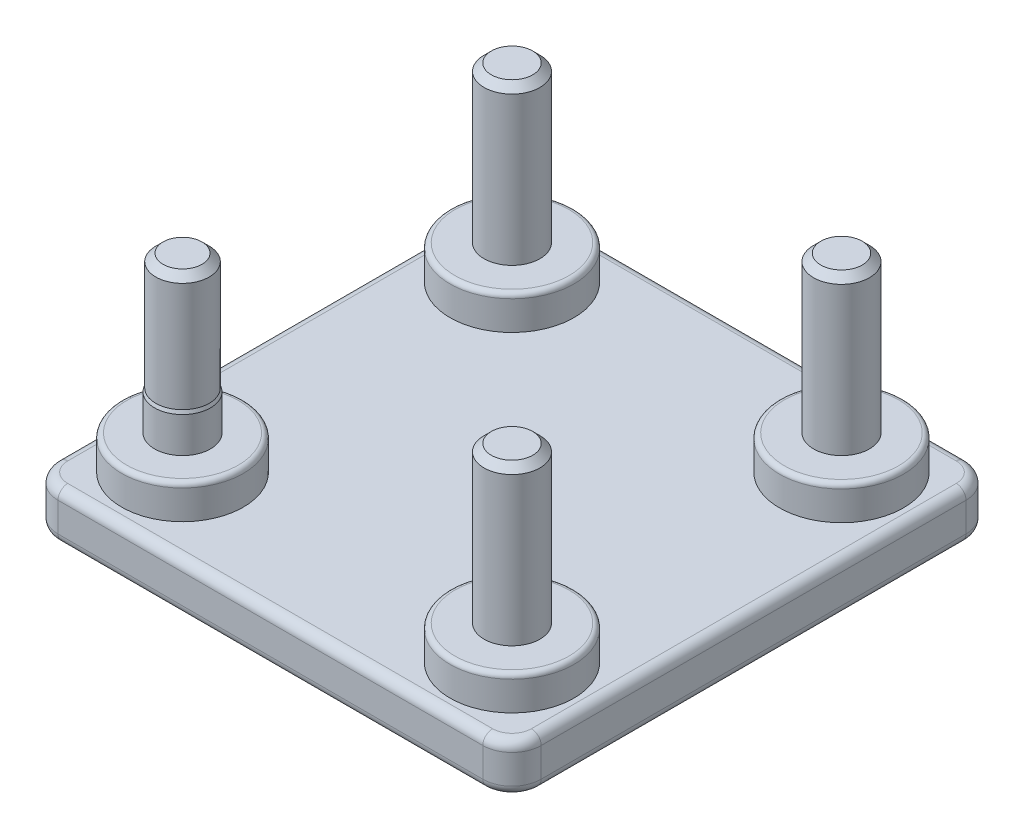
SolidWorks part; units mm, degrees
ref_plane "Front Plane" through (0, 0, 0) normal (0, 0, 1) x (1, 0, 0)
ref_plane "Top Plane" through (0, 0, 0) normal (0, 1, 0) x (1, 0, 0)
ref_plane "Right Plane" through (0, 0, 0) normal (1, 0, 0) x (0, 0, -1)
sketch "Sketch1" plane through (0, 0, 0) normal (0, 1, 0) x (1, 0, 0)
  line L1 (0.1721, 16.4036) -> (49.8471, 16.4036)
  line L2 (0.1721, 16.4036) -> (0.1721, 66.0786)
  line L3 (0.1721, 66.0786) -> (49.8471, 66.0786)
  line L4 (49.8471, 16.4036) -> (49.8471, 66.0786)
  line L8 (14.7548, 29.4959) -> (35.2548, 29.4959)
  line L9 (13.2548, 51.4959) -> (13.2548, 30.9959)
  line L10 (35.2548, 52.9959) -> (14.7548, 52.9959)
  line L11 (36.7548, 30.9959) -> (36.7548, 51.4959)
  line L12 (14.7548, 29.4959) -> (35.2548, 29.4959) construction
  line L13 (13.2548, 51.4959) -> (13.2548, 30.9959) construction
  line L14 (35.2548, 52.9959) -> (14.7548, 52.9959) construction
  line L15 (36.7548, 30.9959) -> (36.7548, 51.4959) construction
  line L16 (14.0048, 34.5935) -> (18.0048, 34.5935)
  line L17 (14.0048, 47.8007) -> (14.0048, 34.5935)
  line L18 (18.0048, 47.8007) -> (14.0048, 47.8007)
  line L19 (18.0048, 34.5935) -> (18.0048, 47.8007)
  line L20 (14.0048, 34.5935) -> (18.0048, 34.5935) construction
  line L21 (14.0048, 47.8007) -> (14.0048, 34.5935) construction
  line L22 (18.0048, 47.8007) -> (14.0048, 47.8007) construction
  line L23 (18.0048, 34.5935) -> (18.0048, 47.8007) construction
  line L24 (32.0048, 34.5935) -> (36.0048, 34.5935)
  line L25 (36.0048, 34.5935) -> (36.0048, 47.8007)
  line L26 (36.0048, 47.8007) -> (32.0048, 47.8007)
  line L27 (32.0048, 47.8007) -> (32.0048, 34.5935)
  line L28 (32.0048, 34.5935) -> (36.0048, 34.5935) construction
  line L29 (36.0048, 34.5935) -> (36.0048, 47.8007) construction
  line L30 (36.0048, 47.8007) -> (32.0048, 47.8007) construction
  line L31 (32.0048, 47.8007) -> (32.0048, 34.5935) construction
  line L32 (30.1074, 36.5249) -> (31.1807, 36.5249)
  line L33 (30.1074, 45.8309) -> (30.1074, 36.5249)
  line L34 (31.1807, 45.8309) -> (30.1074, 45.8309)
  line L35 (31.1807, 36.5249) -> (31.1807, 45.8309)
  line L36 (30.1074, 36.5249) -> (31.1807, 36.5249) construction
  line L37 (30.1074, 45.8309) -> (30.1074, 36.5249) construction
  line L38 (31.1807, 45.8309) -> (30.1074, 45.8309) construction
  line L39 (31.1807, 36.5249) -> (31.1807, 45.8309) construction
  line L40 (18.0048, 37.8287) -> (22.2111, 37.8287)
  line L41 (18.0048, 44.6472) -> (18.0048, 37.8287)
  line L42 (22.2111, 44.6472) -> (18.0048, 44.6472)
  line L43 (22.2111, 37.8287) -> (22.2111, 44.6472)
  line L44 (18.0048, 37.8287) -> (22.2111, 37.8287) construction
  line L45 (18.0048, 44.6472) -> (18.0048, 37.8287) construction
  line L46 (22.2111, 44.6472) -> (18.0048, 44.6472) construction
  line L47 (22.2111, 37.8287) -> (22.2111, 44.6472) construction
  line L48 (38.7548, 30.9959) -> (38.7548, 51.4959)
  line L49 (14.7548, 27.4959) -> (35.2548, 27.4959)
  line L50 (11.2548, 51.4959) -> (11.2548, 30.9959)
  line L51 (35.2548, 54.9959) -> (14.7548, 54.9959)
  line L52 (38.7548, 30.9959) -> (38.7548, 51.4959) construction
  line L53 (14.7548, 27.4959) -> (35.2548, 27.4959) construction
  line L54 (11.2548, 51.4959) -> (11.2548, 30.9959) construction
  line L55 (35.2548, 54.9959) -> (14.7548, 54.9959) construction
  circle A1 centre (8.0673, 58.1834) radius 6
  circle A2 centre (8.0673, 58.1834) radius 6 construction
  circle A3 centre (25.0048, 41.2459) radius 23
  circle A4 centre (25.0048, 41.2459) radius 23 construction
  circle A5 centre (8.0673, 58.1834) radius 3.125
  circle A6 centre (8.0673, 58.1834) radius 3.125 construction
  circle A7 centre (8.0673, 24.3084) radius 6
  circle A8 centre (8.0673, 24.3084) radius 6 construction
  circle A9 centre (8.0673, 24.3084) radius 3.125
  circle A10 centre (8.0673, 24.3084) radius 3.125 construction
  circle A11 centre (41.9423, 24.3084) radius 3.125
  circle A12 centre (41.9423, 24.3084) radius 3.125 construction
  circle A13 centre (41.9423, 24.3084) radius 6
  circle A14 centre (41.9423, 24.3084) radius 6 construction
  circle A15 centre (41.9423, 58.1834) radius 6
  circle A16 centre (41.9423, 58.1834) radius 6 construction
  circle A17 centre (41.9423, 58.1834) radius 3.125
  circle A18 centre (41.9423, 58.1834) radius 3.125 construction
  circle A19 centre (16.3548, 32.5959) radius 1.125
  circle A20 centre (16.3548, 32.5959) radius 1.125 construction
  circle A21 centre (33.6548, 32.5959) radius 1.125
  circle A22 centre (33.6548, 32.5959) radius 1.125 construction
  circle A23 centre (16.3548, 49.8959) radius 1.125
  circle A24 centre (16.3548, 49.8959) radius 1.125 construction
  circle A25 centre (33.6548, 49.8959) radius 1.125
  arc A26 (13.2548, 30.9959) -> (14.7548, 29.4959) centre (14.7548, 30.9959) ccw
  arc A27 (14.7548, 52.9959) -> (13.2548, 51.4959) centre (14.7548, 51.4959) ccw
  arc A28 (36.7548, 51.4959) -> (35.2548, 52.9959) centre (35.2548, 51.4959) ccw
  arc A29 (35.2548, 29.4959) -> (36.7548, 30.9959) centre (35.2548, 30.9959) ccw
  arc A30 (13.2548, 30.9959) -> (14.7548, 29.4959) centre (14.7548, 30.9959) ccw construction
  arc A31 (14.7548, 52.9959) -> (13.2548, 51.4959) centre (14.7548, 51.4959) ccw construction
  arc A32 (36.7548, 51.4959) -> (35.2548, 52.9959) centre (35.2548, 51.4959) ccw construction
  arc A33 (35.2548, 29.4959) -> (36.7548, 30.9959) centre (35.2548, 30.9959) ccw construction
  circle A34 centre (33.6548, 49.8959) radius 1.125 construction
  arc A38 (38.7548, 51.4959) -> (35.2548, 54.9959) centre (35.2548, 51.4959) ccw
  arc A39 (35.2548, 27.4959) -> (38.7548, 30.9959) centre (35.2548, 30.9959) ccw
  arc A40 (11.2548, 30.9959) -> (14.7548, 27.4959) centre (14.7548, 30.9959) ccw
  arc A41 (14.7548, 54.9959) -> (11.2548, 51.4959) centre (14.7548, 51.4959) ccw
  arc A42 (38.7548, 51.4959) -> (35.2548, 54.9959) centre (35.2548, 51.4959) ccw construction
  arc A43 (35.2548, 27.4959) -> (38.7548, 30.9959) centre (35.2548, 30.9959) ccw construction
  arc A44 (11.2548, 30.9959) -> (14.7548, 27.4959) centre (14.7548, 30.9959) ccw construction
  arc A45 (14.7548, 54.9959) -> (11.2548, 51.4959) centre (14.7548, 51.4959) ccw construction
  dimension "D20" = 7.9048
  dimension "D21" = 7.9048
  dimension "D22" = 49.675
  dimension "D23" = 49.675
  dimension "D24" = 49.675
  dimension "D1" = 0
  dimension "D2" = 0
  dimension "D3" = 0
  dimension "D4" = 0
  dimension "D5" = 0
  dimension "D6" = 0
  dimension "D7" = 0
  dimension "D8" = 0
  dimension "D9" = 0
  dimension "D10" = 0
  dimension "D11" = 0
  dimension "D12" = 0
  dimension "D13" = 0
  dimension "D14" = 0
  dimension "D15" = 0
  dimension "D16" = 0
  dimension "D17" = 0
  dimension "D18" = 0
  dimension "D19" = 0
extrude "Boss-Extrude1" add sketch "Sketch1" along normal blind 5
sketch "Sketch3" plane through (0, 0, 0) normal (0, 1, 0) x (1, 0, 0)
  circle A0 centre (8.0673, 58.1834) radius 4
  circle A1 centre (41.9423, 58.1834) radius 4
  circle A2 centre (41.9423, 24.3084) radius 4
  circle A3 centre (8.0673, 24.3084) radius 4
  circle A4 centre (8.0673, 24.3084) radius 4.275
  circle A5 centre (41.9423, 24.3084) radius 4.275
  circle A6 centre (41.9423, 58.1834) radius 4.275
  circle A7 centre (8.0673, 58.1834) radius 4.275
  dimension "D1" = 8
  dimension "D2" = 8
  dimension "D3" = 8
  dimension "D4" = 8
  dimension "D5" = 8.55
  dimension "D6" = 8.55
  dimension "D7" = 8.55
  dimension "D8" = 8.55
extrude "Cut-Extrude1" cut sketch "Sketch3" along normal up to next from offset 1 contours A5 | A6 | A4 | A7
sketch "Sketch2" plane through (0, 0, 0) normal (0, 1, 0) x (1, 0, 0)
  line L0 (17.374, 45.7096) -> (5.2059, 45.7096) construction
  circle A0 centre (8.0673, 24.3084) radius 2.875
  circle A4 centre (41.9423, 58.1834) radius 2.875
  circle A5 centre (41.9423, 24.3084) radius 2.875
  circle A6 centre (8.0673, 24.3084) radius 2.75
  circle A7 centre (8.0673, 58.1834) radius 2.875
  circle A8 centre (41.9423, 58.1834) radius 6.375
  circle A9 centre (41.9423, 24.3084) radius 6.375
  circle A10 centre (8.0673, 24.3084) radius 6.25
  circle A11 centre (8.0673, 58.1834) radius 6.375
  dimension "D2" = 5.75
  dimension "D3" = 5.75
  dimension "D4" = 5.5
  dimension "D5" = 5.75
  dimension "D6" = 5.75
  dimension "D1" = 3.5
extrude "Boss-Extrude2" add sketch "Sketch2" along normal blind 3.5 from surface separate body contours A11 | A10 | A9 | A8 starting at face at (41.9423, 5, -62.4584)
extrude "Boss-Extrude3" add sketch "Sketch2<3>" along normal blind 16 from surface contours A7 | A4 | A5 | A6 region at (41.9423, 0, -58.1834) region at (41.9423, 0, -24.3084) region at (8.0673, 0, -24.3084) region at (8.0673, 0, -58.1834) starting at face at (8.0673, 8.5, -64.5584)
sketch "Sketch2<3>" plane through (0, 0, 0) normal (0, 1, 0) x (1, 0, 0) same geometry as "Sketch2"
extrude "Boss-Extrude4" add sketch "Sketch3<2>" against normal blind 1.875 from surface contours A0 | A3 | A1 | A2 starting at face at (8.0673, 5, -30.5584)
sketch "Sketch3<2>" plane through (0, 0, 0) normal (0, 1, 0) x (1, 0, 0) same geometry as "Sketch3"
extrude "Boss-Extrude5" add sketch "Sketch2<4>" along normal blind 4 from surface contours A0 starting at face at (8.0673, 8.5, -27.0584)
sketch "Sketch2<4>" plane through (0, 0, 0) normal (0, 1, 0) x (1, 0, 0) same geometry as "Sketch2"
chamfer "Chamfer6" distance 0.125 angle 70 1 edges at (8.0673, 12.5, -27.1834) first distance on face at (8.0673, 12.5, -27.0584)
chamfer "Chamfer1" distance 0.75 angle 45 4 edges at (41.9423, 5, -62.4584) (41.9423, 5, -28.5834) (8.0673, 5, -28.5834) (8.0673, 5, -62.4584)
fillet "Fillet5" radius 3 4 edges at (49.8471, 2.5, -16.4036) (49.8471, 2.5, -66.0786) (0.1721, 2.5, -66.0786) (0.1721, 2.5, -16.4036)
fillet "Fillet6" radius 1 16 edges at (1.0508, 0, -17.2822) (0.1721, 0, -41.2411) (1.0508, 0, -65.1999) (25.0096, 0, -66.0786) (48.9684, 0, -65.1999) (49.8471, 0, -41.2411) (48.9684, 0, -17.2822) (1.0508, 5, -17.2822) (0.1721, 5, -41.2411) (1.0508, 5, -65.1999) (25.0096, 5, -66.0786) (48.9684, 5, -65.1999) (49.8471, 5, -41.2411) (48.9684, 5, -17.2822) (25.0096, 0, -16.4036) (25.0096, 5, -16.4036)
fillet "Fillet1" radius 0.5 1 edges at (8.0673, 8.5, -30.5584)
fillet "Fillet2" radius 0.5 1 edges at (41.9423, 8.5, -30.6834)
fillet "Fillet3" radius 0.5 1 edges at (8.0673, 8.5, -64.5584)
fillet "Fillet4" radius 0.5 1 edges at (41.9423, 8.5, -64.5584)
chamfer "Chamfer2" distance 0.75 angle 45 1 edges at (8.0673, 24.5, -27.0584)
chamfer "Chamfer3" distance 0.75 angle 45 1 edges at (8.0673, 24.5, -61.0584)
chamfer "Chamfer4" distance 0.75 angle 45 1 edges at (41.9423, 24.5, -61.0584)
chamfer "Chamfer5" distance 0.75 angle 45 1 edges at (41.9423, 24.5, -27.1834)
